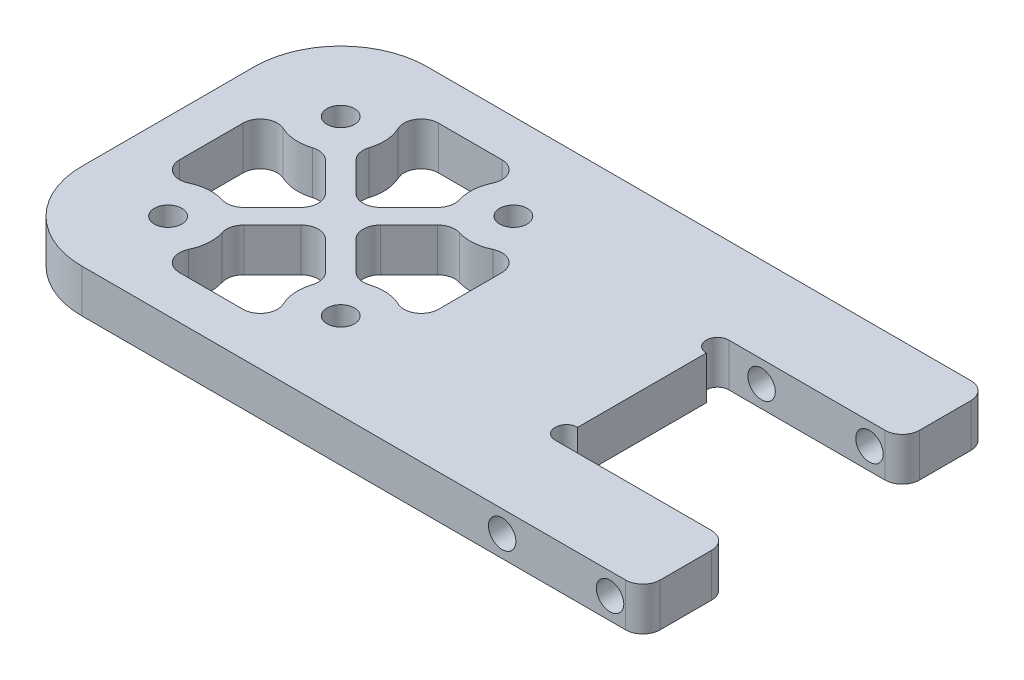
SolidWorks part; units mm, degrees
material "6061-T6 (SS)"
ref_plane "Front Plane" through (0, 0, 0) normal (0, 0, 1) x (1, 0, 0)
ref_plane "Top Plane" through (0, 0, 0) normal (0, 1, 0) x (1, 0, 0)
ref_plane "Right Plane" through (0, 0, 0) normal (1, 0, 0) x (0, 0, -1)
sketch "Sketch1" plane through (0, 0, 0) normal (0, 1, 0) x (1, 0, 0)
  line L0 (34.925, 25.4) -> (60.325, 25.4)
  line L1 (-34.925, -25.4) -> (34.925, -25.4)
  line L2 (-34.925, -25.4) -> (-34.925, 25.4)
  line L3 (-34.925, 25.4) -> (34.925, 25.4)
  line L5 (-34.925, -25.4) -> (34.925, 25.4) construction
  line L6 (-34.925, 25.4) -> (34.925, -25.4) construction
  line L7 (60.325, 25.4) -> (60.325, -25.4)
  line L8 (60.325, -25.4) -> (34.925, -25.4)
  point P0 (0, 0)
  dimension "D1" = 69.85
  dimension "D2" = 50.8
  dimension "D3" = 25.4
extrude "Boss-Extrude1" add sketch "Sketch1" along normal blind 6.35
sketch "Sketch2" plane through (0, 6.35, 0) normal (0, 1, 0) x (1, 0, 0)
  line L4 (60.325, 25.4) -> (-34.925, 25.4) construction
  line L5 (-34.925, -25.4) -> (60.325, -25.4) construction
  line L7 (15.875, 25.4) -> (15.875, -25.4) construction
  line L8 (-34.925, 25.4) -> (-34.925, -25.4) construction
  dimension "D1" = 50.8
hole_wizard "#10-32 Tapped Hole2" positions "Sketch3" profile "Sketch4" tap size "#10-32" standard "ANSI Inch" end condition through all
sketch "Sketch3" plane through (0, 6.35, 0) normal (0, 1, 0) x (1, 0, 0)
  line L4 (-22.225, 25.4) -> (-22.225, -25.4) construction
  line L5 (60.325, 25.4) -> (-34.925, 25.4) construction
  line L6 (-34.925, -25.4) -> (60.325, -25.4) construction
  line L8 (3.175, 25.4) -> (3.175, -25.4) construction
  line L9 (-34.925, 25.4) -> (-34.925, -25.4) construction
  line L11 (-34.925, 12.7) -> (15.875, 12.7) construction
  line L13 (-34.925, -12.7) -> (15.875, -12.7) construction
  point P0 (-22.225, 12.7)
  point P2 (3.175, 12.7)
  point P4 (3.175, -12.7)
  point P6 (-22.225, -12.7)
  dimension "D1" = 12.7
  dimension "D2" = 38.1
  dimension "D3" = 12.7
  dimension "D4" = 12.7
  dimension "D5" = 50.8
  dimension "D6" = 50.8
sketch "Sketch4" plane through (-22.225, 6.35, -12.7) normal (1, 0, 0) x (0, 0, 1)
  line L0 (0, 0) -> (0, 6.35)
  line L1 (0, 6.35) -> (2.0193, 6.35)
  line L2 (2.0193, 6.35) -> (2.0193, 0)
  line L5 (2.0193, 0) -> (0, 0)
  line L11 (0, -6.35) -> (0, 107.95) construction
  dimension "Thru Tap Drill Dia." = 4.0386
  dimension "Thru Tap Drill Depth" = 6.35
cosmetic thread "Hole Thread3" parameters "D2"=4.826
cosmetic thread "Hole Thread4" parameters "D2"=4.826
cosmetic thread "Hole Thread5" parameters "D2"=4.826
cosmetic thread "Hole Thread6" parameters "D2"=4.826
sketch "Sketch5" plane through (0, 6.35, 0) normal (0, 1, 0) x (1, 0, 0)
  line L1 (60.325, -25.4) -> (60.325, 25.4) construction
  line L2 (34.798, -12.7635) -> (60.325, -12.7635)
  line L4 (34.798, -12.7635) -> (34.798, 12.7635)
  line L5 (34.798, 12.7635) -> (60.325, 12.7635)
  line L6 (60.325, -12.7635) -> (60.325, 12.7635)
  line L7 (34.798, -12.7635) -> (60.325, 12.7635) construction
  line L8 (34.798, 12.7635) -> (60.325, -12.7635) construction
  line L13 (60.325, 12.7635) -> (60.325, 25.4) construction
  line L14 (60.325, -12.7635) -> (60.325, -25.4) construction
  dimension "D3" = 25.527
extrude "Cut-Extrude1" cut sketch "Sketch5" against normal through all
sketch "Sketch6" plane through (0, 6.35, 0) normal (0, 1, 0) x (1, 0, 0)
  line L0 (34.798, 12.7635) -> (34.798, -12.7635) construction
  line L1 (34.798, 9.4615) -> (34.798, 12.7635)
  line L2 (34.798, 0) -> (41.7316, 0) construction
  line L3 (34.798, -9.4615) -> (34.798, -12.7635)
  arc A0 (34.798, 12.7635) -> (34.798, 9.4615) centre (34.798, 11.1125) ccw
  arc A1 (34.798, -12.7635) -> (34.798, -9.4615) centre (34.798, -11.1125) cw
  dimension "D1" = 3.302
extrude "Cut-Extrude2" cut sketch "Sketch6" against normal through all
fillet "Fillet1" radius 2.54 4 edges at (60.325, 3.175, 12.7635) (60.325, 3.175, -12.7635) (60.325, 3.175, -25.4) (60.325, 3.175, 25.4)
fillet "Fillet2" radius 12.7 2 edges at (-34.925, 3.175, -25.4) (-34.925, 3.175, 25.4)
sketch "Sketch10" plane through (0, 0, 25.4) normal (0, 0, 1) x (1, 0, 0)
  line L2 (34.798, 6.35) -> (39.624, 3.175) construction
  line L3 (-22.225, 6.35) -> (57.785, 6.35) construction
  line L8 (55.499, 3.175) -> (60.325, 0) construction
  point P0 (55.499, 3.175)
  point P2 (39.624, 3.175)
  dimension "D1" = 15.875
hole_wizard "#10-32 Tapped Hole1" positions "Sketch10" profile "Sketch9" tap size "#10-32" standard "ANSI Inch" end condition through all
sketch "Sketch9" plane through (55.499, 3.175, 25.4) normal (1, 0, 0) x (0, -1, 0)
  line L0 (0, 0) -> (0, 50.8)
  line L1 (0, 50.8) -> (2.0193, 50.8)
  line L2 (2.0193, 50.8) -> (2.0193, 0)
  line L5 (2.0193, 0) -> (0, 0)
  line L11 (0, -6.35) -> (0, 107.95) construction
  dimension "Thru Tap Drill Dia." = 4.0386
  dimension "Thru Tap Drill Depth" = 50.8
cosmetic thread "Hole Thread1" parameters "D2"=4.826
cosmetic thread "Hole Thread2" parameters "D2"=4.826
sketch "Sketch11" plane through (0, 6.35, 0) normal (0, 1, 0) x (1, 0, 0)
  line L0 (-22.225, 19.05) -> (3.175, 19.05)
  line L1 (9.525, -12.7) -> (9.525, 12.7)
  line L2 (-28.575, 12.7) -> (-28.575, -12.7)
  line L3 (-22.225, -19.05) -> (3.175, -19.05)
  line L4 (-19, -7.2299) -> (-11.7701, 0)
  line L5 (-0.05, 7.2299) -> (-7.2799, 0)
  line L6 (-19, 7.2299) -> (-11.7701, 0)
  line L7 (-0.05, -7.2299) -> (-7.2799, 0)
  line L8 (-9.525, 2.2451) -> (-2.2951, 9.475)
  line L9 (-9.525, -2.2451) -> (-16.7549, -9.475)
  line L10 (-9.525, 2.2451) -> (-16.7549, 9.475)
  line L11 (-9.525, -2.2451) -> (-2.2951, -9.475)
  arc A0 (-16.7549, 9.475) -> (-22.225, 19.05) centre (-22.225, 12.7) ccw
  arc A1 (-0.05, 7.2299) -> (9.525, 12.7) centre (3.175, 12.7) ccw
  arc A2 (-2.2951, -9.475) -> (3.175, -19.05) centre (3.175, -12.7) ccw
  arc A3 (-19, -7.2299) -> (-28.575, -12.7) centre (-22.225, -12.7) ccw
  arc A4 (-22.225, -19.05) -> (-16.7549, -9.475) centre (-22.225, -12.7) ccw
  arc A5 (-28.575, 12.7) -> (-19, 7.2299) centre (-22.225, 12.7) ccw
  arc A6 (3.175, 19.05) -> (-2.2951, 9.475) centre (3.175, 12.7) ccw
  arc A7 (9.525, -12.7) -> (-0.05, -7.2299) centre (3.175, -12.7) ccw
  dimension "D1" = 12.7
  dimension "D2" = 3.175
  dimension "D3" = 3.175
extrude "Cut-Extrude3" cut sketch "Sketch11" against normal through all
fillet "Fillet3" radius 2.54 20 edges at (9.525, 3.175, -12.7) (9.525, 3.175, 12.7) (-0.05, 3.175, 7.2299) (-7.2799, 3.175, 0) (-0.05, 3.175, -7.2299) (-22.225, 3.175, -19.05) (3.175, 3.175, -19.05) (-2.2951, 3.175, -9.475) (-9.525, 3.175, -2.2451) (-11.7701, 3.175, 0) (-19, 3.175, 7.2299) (-28.575, 3.175, 12.7) (-28.575, 3.175, -12.7) (-19, 3.175, -7.2299) (-16.7549, 3.175, 9.475) (-9.525, 3.175, 2.2451) (-2.2951, 3.175, 9.475) (3.175, 3.175, 19.05) (-22.225, 3.175, 19.05) (-16.7549, 3.175, -9.475)
